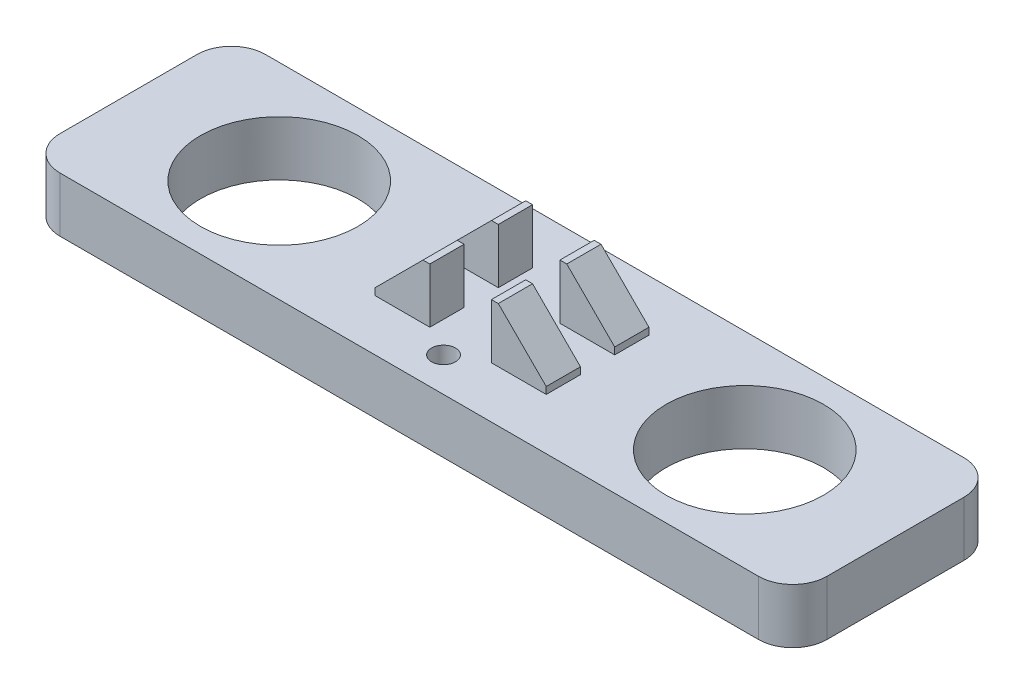
SolidWorks part; units mm, degrees
ref_plane "Front Plane" through (0, 0, 0) normal (0, 0, 1) x (1, 0, 0)
ref_plane "Top Plane" through (0, 0, 0) normal (0, 1, 0) x (1, 0, 0)
ref_plane "Right Plane" through (0, 0, 0) normal (1, 0, 0) x (0, 0, -1)
sketch "Sketch1" plane through (0, 0, 0) normal (0, 1, 0) x (1, 0, 0)
  line L1 (0, 0) -> (60, 0)
  line L2 (0, 0) -> (0, 30)
  line L3 (0, 30) -> (60, 30)
  line L4 (60, 0) -> (60, 30)
  circle A0 centre (22, 15) radius 11.5
  point P7 (0, 15)
  dimension "D3" = 23
  dimension "D4" = 22
  dimension "D1" = 60
  dimension "D2" = 30
extrude "Boss-Extrude1" add sketch "Sketch1" along normal blind 5
sketch "Sketch2" plane through (0, 5, 0) normal (0, 1, 0) x (1, 0, 0)
  line L0 (60, 0) -> (60, 30) construction
  line L1 (0, 0) -> (60, 0) construction
  line L2 (60, 30) -> (0, 30) construction
  circle A0 centre (56, 25) radius 1.75
  circle A1 centre (56, 5) radius 1.75
  dimension "D1" = 3.5
  dimension "D4" = 5
  dimension "D2" = 4
  dimension "D3" = 5
extrude "Cut-Extrude1" cut sketch "Sketch2" against normal through all
fillet "Fillet1" radius 5 2 edges at (0, 2.5, 0) (0, 2.5, -30)
sketch "Sketch6" plane through (0, 0, 0) normal (0, -1, 0) x (1, 0, 0)
  line L12 (60, 0) -> (5, 0)
  line L13 (0, -5) -> (0, -25)
  line L14 (5, -30) -> (60, -30)
  line L15 (60, -30) -> (60, 0)
  line L18 (60, 0) -> (5, 0)
  line L19 (0, -5) -> (0, -25)
  line L20 (5, -30) -> (60, -30)
  line L21 (60, -30) -> (60, 0)
  arc A8 (5, 0) -> (0, -5) centre (5, -5) ccw
  arc A9 (0, -25) -> (5, -30) centre (5, -25) ccw
  arc A12 (5, 0) -> (0, -5) centre (5, -5) ccw
  arc A13 (0, -25) -> (5, -30) centre (5, -25) ccw
  circle M11 centre (56, -25) radius 1.75
  circle M12 centre (56, -5) radius 1.75
  line M13 (60, 0) -> (5, 0)
  arc M14 (5, 0) -> (0, -5) centre (5, -5) ccw
  line M15 (0, -5) -> (0, -25)
  arc M16 (0, -25) -> (5, -30) centre (5, -25) ccw
  line M17 (5, -30) -> (60, -30)
  line M18 (60, -30) -> (60, 0)
  line M22 (60, -30) -> (60, 0)
  circle M23 centre (22, -15) radius 11.5
  dimension "D1" = 0
extrude "Boss-Extrude4" add sketch "Sketch6" along normal blind 3 contours M22 M13 M14 M15 M16 M17 M18 M12 M23 M11 region at (59.3292, 0, -15)
ref_plane "Plane1" through (56, 0, 0) normal (1, 0, 0) x (0, 0, -1)
mirror "Mirror1" about plane through (56, 0, 0) normal (1, 0, 0) of "Boss-Extrude4", "Fillet1", "Cut-Extrude1", "Boss-Extrude1"
sketch "Sketch7" plane through (0, 5, 0) normal (0, 1, 0) x (1, 0, 0)
  line L0 (0, 25) -> (0, 5) construction
  line L1 (43.5, 22.5) -> (51.5, 22.5)
  line L2 (43.5, 22.5) -> (43.5, 17.5)
  line L3 (43.5, 17.5) -> (51.5, 17.5)
  line L4 (51.5, 22.5) -> (51.5, 17.5)
  line L5 (60.5, 22.5) -> (68.5, 22.5)
  line L6 (60.5, 22.5) -> (60.5, 17.5)
  line L7 (60.5, 17.5) -> (68.5, 17.5)
  line L8 (68.5, 22.5) -> (68.5, 17.5)
  line L9 (5, 0) -> (107, 0) construction
  line L10 (107, 30) -> (5, 30) construction
  point P8 (0, 15)
  point P9 (51.5, 20)
  point P12 (56, 0)
  point P13 (43.5, 20)
  dimension "D1" = 9
  dimension "D2" = 5
  dimension "D3" = 8
  dimension "D4" = 4.5
  dimension "D5" = 7.5
extrude "Boss-Extrude5" add sketch "Sketch7" along normal blind 8
chamfer "Chamfer1" distance 7 angle 45 2 edges at (68.5, 13, -20) (43.5, 13, -20)
ref_plane "Plane2" through (0, 0, -15) normal (0, 0, -1) x (-1, 0, 0)
mirror "Mirror2" about plane through (0, 0, -15) normal (0, 0, -1) of "Chamfer1", "Boss-Extrude5"
